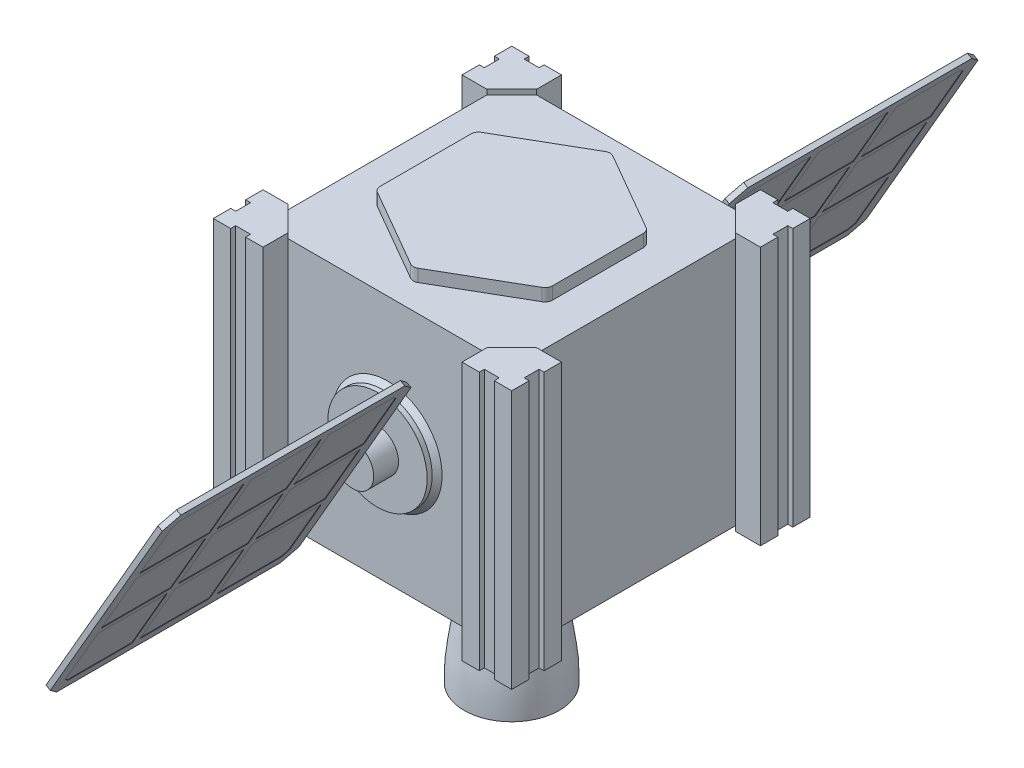
SolidWorks part; units mm, degrees
ref_plane "Front Plane" through (0, 0, 0) normal (0, 0, 1) x (1, 0, 0)
ref_plane "Top Plane" through (0, 0, 0) normal (0, 1, 0) x (1, 0, 0)
ref_plane "Right Plane" through (0, 0, 0) normal (1, 0, 0) x (0, 0, -1)
sketch "Sketch2" plane through (0, 0, 0) normal (0, 1, 0) x (1, 0, 0)
  line L1 (63.5, -63.5) -> (-63.5, -63.5)
  line L2 (63.5, -63.5) -> (63.5, 63.5)
  line L3 (63.5, 63.5) -> (-63.5, 63.5)
  line L4 (-63.5, -63.5) -> (-63.5, 63.5)
  line L5 (63.5, -63.5) -> (-63.5, 63.5) construction
  line L6 (63.5, 63.5) -> (-63.5, -63.5) construction
  line L7 (-50.8, 50.8) -> (-76.2, 50.8)
  line L8 (-50.8, 50.8) -> (-50.8, 76.2)
  line L9 (-50.8, 76.2) -> (-76.2, 76.2)
  line L10 (-76.2, 50.8) -> (-76.2, 76.2)
  line L11 (-50.8, 50.8) -> (-76.2, 76.2) construction
  line L12 (-50.8, 76.2) -> (-76.2, 50.8) construction
  line L13 (50.8, 50.8) -> (76.2, 50.8)
  line L14 (50.8, 50.8) -> (50.8, 76.2)
  line L15 (50.8, 76.2) -> (76.2, 76.2)
  line L16 (76.2, 50.8) -> (76.2, 76.2)
  line L17 (50.8, 50.8) -> (76.2, 76.2) construction
  line L18 (50.8, 76.2) -> (76.2, 50.8) construction
  line L19 (76.2, -50.8) -> (50.8, -50.8)
  line L20 (76.2, -50.8) -> (76.2, -76.2)
  line L21 (76.2, -76.2) -> (50.8, -76.2)
  line L22 (50.8, -50.8) -> (50.8, -76.2)
  line L23 (76.2, -50.8) -> (50.8, -76.2) construction
  line L24 (76.2, -76.2) -> (50.8, -50.8) construction
  line L25 (-50.8, -50.8) -> (-76.2, -50.8)
  line L26 (-50.8, -50.8) -> (-50.8, -76.2)
  line L27 (-50.8, -76.2) -> (-76.2, -76.2)
  line L28 (-76.2, -50.8) -> (-76.2, -76.2)
  line L29 (-50.8, -50.8) -> (-76.2, -76.2) construction
  line L30 (-50.8, -76.2) -> (-76.2, -50.8) construction
  point P0 (0, 0)
  dimension "D1" = 25.4
  dimension "D2" = 25.4
  dimension "D3" = 127
  dimension "D4" = 127
  dimension "D5" = 25.4
  dimension "D6" = 25.4
  dimension "D7" = 25.4
extrude "Boss-Extrude1" add sketch "Sketch2" along normal blind 127 contours L10 L7 L4 L3 L8 L9 | L7 L8 L3 L4 | L14 L13 L2 L3 | L13 L16 L15 L14 L3 L2 | L1 L22 L21 L20 L19 L2 | L25 L28 L27 L26 L1 L4 | L26 L25 L4 L1 | L25 L26 L1 L22 L19 L2 L13 L14 L3 L8 L7 L4 | L19 L22 L1 L2 region at (65.6167, 0, 65.6167) region at (57.15, 0, 57.15) region at (0, 0, 0) region at (-65.6167, 0, 65.6167) region at (-57.15, 0, 57.15) region at (57.15, 0, -57.15) region at (65.6167, 0, -65.6167) region at (-65.6167, 0, -65.6167) region at (-57.15, 0, -57.15)
sketch "Sketch3" plane through (0, 0, 0) normal (0, -1, 0) x (1, 0, 0)
  line L0 (-50.8, 63.5) -> (-63.5, 50.8)
  line L1 (50.8, 63.5) -> (63.5, 50.8)
  line L2 (63.5, -50.8) -> (50.8, -63.5)
  line L3 (-63.5, -50.8) -> (-50.8, -63.5)
  line L20 (-63.5, 50.8) -> (-63.5, -50.8)
  line L21 (-63.5, -50.8) -> (-76.2, -50.8)
  line L22 (-76.2, -50.8) -> (-76.2, -76.2)
  line L23 (-76.2, -76.2) -> (-50.8, -76.2)
  line L24 (-50.8, -76.2) -> (-50.8, -63.5)
  line L25 (-50.8, -63.5) -> (50.8, -63.5)
  line L26 (50.8, -63.5) -> (50.8, -76.2)
  line L27 (50.8, -76.2) -> (76.2, -76.2)
  line L28 (76.2, -76.2) -> (76.2, -50.8)
  line L29 (76.2, -50.8) -> (63.5, -50.8)
  line L30 (63.5, -50.8) -> (63.5, 50.8)
  line L31 (63.5, 50.8) -> (76.2, 50.8)
  line L32 (76.2, 50.8) -> (76.2, 76.2)
  line L33 (76.2, 76.2) -> (50.8, 76.2)
  line L34 (50.8, 76.2) -> (50.8, 63.5)
  line L35 (50.8, 63.5) -> (-50.8, 63.5)
  line L36 (-50.8, 63.5) -> (-50.8, 76.2)
  line L37 (-50.8, 76.2) -> (-76.2, 76.2)
  line L38 (-76.2, 76.2) -> (-76.2, 50.8)
  line L39 (-76.2, 50.8) -> (-63.5, 50.8)
  line L40 (-63.5, 50.8) -> (-63.5, -50.8)
  line L41 (-63.5, -50.8) -> (-76.2, -50.8)
  line L42 (-76.2, -50.8) -> (-76.2, -76.2)
  line L43 (-76.2, -76.2) -> (-50.8, -76.2)
  line L44 (-50.8, -76.2) -> (-50.8, -63.5)
  line L45 (-50.8, -63.5) -> (50.8, -63.5)
  line L46 (50.8, -63.5) -> (50.8, -76.2)
  line L47 (50.8, -76.2) -> (76.2, -76.2)
  line L48 (76.2, -76.2) -> (76.2, -50.8)
  line L49 (76.2, -50.8) -> (63.5, -50.8)
  line L50 (63.5, -50.8) -> (63.5, 50.8)
  line L51 (63.5, 50.8) -> (76.2, 50.8)
  line L52 (76.2, 50.8) -> (76.2, 76.2)
  line L53 (76.2, 76.2) -> (50.8, 76.2)
  line L54 (50.8, 76.2) -> (50.8, 63.5)
  line L55 (50.8, 63.5) -> (-50.8, 63.5)
  line L56 (-50.8, 63.5) -> (-50.8, 76.2)
  line L57 (-50.8, 76.2) -> (-76.2, 76.2)
  line L58 (-76.2, 76.2) -> (-76.2, 50.8)
  line L59 (-76.2, 50.8) -> (-63.5, 50.8)
  arc A0 (-50.8, -63.5) -> (-50.8, -65.3363) centre (-51.7181, -64.4181) cw
  line M22 (-63.5, -50.8) -> (-76.2, -50.8)
  line M23 (-76.2, -50.8) -> (-76.2, -76.2)
  line M24 (-76.2, -76.2) -> (-50.8, -76.2)
  line M25 (-50.8, -76.2) -> (-50.8, -63.5)
  line M27 (50.8, -63.5) -> (50.8, -76.2)
  line M28 (50.8, -76.2) -> (76.2, -76.2)
  line M29 (76.2, -76.2) -> (76.2, -50.8)
  line M30 (76.2, -50.8) -> (63.5, -50.8)
  line M32 (63.5, 50.8) -> (76.2, 50.8)
  line M33 (76.2, 50.8) -> (76.2, 76.2)
  line M34 (76.2, 76.2) -> (50.8, 76.2)
  line M35 (50.8, 76.2) -> (50.8, 63.5)
  line M37 (-50.8, 63.5) -> (-50.8, 76.2)
  line M38 (-50.8, 76.2) -> (-76.2, 76.2)
  line M39 (-76.2, 76.2) -> (-76.2, 50.8)
  line M40 (-76.2, 50.8) -> (-63.5, 50.8)
  dimension "D1" = 0
extrude "Boss-Extrude2" add sketch "Sketch3" along normal blind 2.54 contours L0 M37 M38 M39 M40 | L1 M35 M32 M33 M34 | L2 M30 M27 M28 M29 | L3 L44 M22 M23 M24 M25 region at (-64.7095, 0, 64.7095) region at (64.7095, 0, 64.7095) region at (-64.7095, 0, -64.7095) region at (64.7095, 0, -64.7095)
ref_plane "Plane1" through (0, 63.5, 0) normal (0, 1, 0) x (1, 0, 0)
mirror "Mirror1" about plane through (0, 63.5, 0) normal (0, 1, 0) of "Boss-Extrude2"
sketch "Sketch5" plane through (0, 129.54, 0) normal (0, 1, 0) x (1, 0, 0)
  line L0 (-76.2, 76.2) -> (-50.8, 76.2) construction
  line L1 (-67.31, 76.2) -> (-59.69, 76.2)
  line L2 (-67.31, 76.2) -> (-67.31, 73.66)
  line L3 (-67.31, 73.66) -> (-59.69, 73.66)
  line L4 (-59.69, 76.2) -> (-59.69, 73.66)
  line L5 (-76.2, 50.8) -> (-76.2, 76.2) construction
  line L6 (-76.2, 67.31) -> (-73.66, 67.31)
  line L7 (-76.2, 67.31) -> (-76.2, 59.69)
  line L8 (-76.2, 59.69) -> (-73.66, 59.69)
  line L9 (-73.66, 67.31) -> (-73.66, 59.69)
  line L10 (-50.8, 63.5) -> (-73.66, 63.5) construction
  line L12 (-63.5, 50.8) -> (-63.5, 73.66) construction
  line L13 (-50.8, 76.2) -> (-50.8, 63.5) construction
  line L15 (-63.5, 50.8) -> (-76.2, 50.8) construction
  dimension "D1" = 7.62
  dimension "D2" = 2.54
extrude "Cut-Extrude1" cut sketch "Sketch5" against normal through all
ref_axis "Axis1" through (0, 136.144, 0) along (0, -1, 0)
pattern_circular "CirPattern1" count 4 over 360 about axis through (0, 136.144, 0) along (0, -1, 0) of "Cut-Extrude1"
sketch "Sketch6" plane through (0, 0, 63.5) normal (0, 0, 1) x (1, 0, 0)
  line L0 (0, 127) -> (0, -3.9486) construction
  line L1 (50.8, 127) -> (-50.8, 127) construction
  circle A0 centre (0, 61.5257) radius 25.4
  dimension "D1" = 50.8
extrude "Boss-Extrude3" add sketch "Sketch6" along normal blind 5.08
chamfer "Chamfer1" distance 2.54 angle 45 1 edges at (25.4, 61.5257, 63.5)
sketch "Sketch7" plane through (0, 0, 68.58) normal (0, 0, 1) x (1, 0, 0)
  line L0 (0, 86.9257) -> (0, 36.1257) construction
  circle A0 centre (0, 61.5257) radius 25.4 construction
  circle A1 centre (0, 61.5257) radius 10.795
  dimension "D1" = 21.59
extrude "Boss-Extrude4" add sketch "Sketch7" along normal blind 12.7
sketch "Sketch8" plane through (0, 0, 81.28) normal (0, 0, 1) x (1, 0, 0)
  line L0 (0, 71.6598) -> (0, 50.7307) construction
  line L1 (0, 61.1953) -> (9.2024, 55.8823) construction
  circle A0 centre (0, 61.5257) radius 10.795 construction
  circle A1 centre (0, 61.5257) radius 10.795 construction
  dimension "D1" = 60
ref_plane "Plane2" through (0, 61.1953, 81.28) normal (0.866, -0.5, 0) x (-0.5, -0.866, 0)
sketch "Sketch9" plane through (0, 61.1953, 81.28) normal (0.866, -0.5, 0) x (-0.5, -0.866, 0)
  line L0 (-11.0812, 0) -> (10.5088, 0) construction
  line L1 (-11.0812, 0) -> (10.5088, 0) construction
  line L2 (-0.2862, 0) -> (-63.7862, 0)
  line L3 (-0.2862, 0) -> (63.2138, 0)
  line L4 (-63.7862, 0) -> (-63.7862, -127)
  line L5 (-63.7862, -127) -> (63.2138, -127)
  line L6 (63.2138, -127) -> (63.2138, 0)
  dimension "D1" = 63.5
  dimension "D2" = 63.5
  dimension "D3" = 127
extrude "Boss-Extrude5" add sketch "Sketch9" along normal blind 1.27 and the other way blind 1.27
chamfer "Chamfer2" distance 6.35 angle 45 4 edges at (-31.6069, 6.4505, 81.28) (31.8931, 116.4357, 81.28) (31.8931, 116.4357, 208.28) (-31.6069, 6.4505, 208.28)
sketch "Sketch11" plane through (-27.5982, 15.9338, 0) normal (-0.866, 0.5, 0) x (0, 0, 1)
  line L0 (87.63, 53.2828) -> (123.19, 53.2828) construction
  line L1 (123.19, 53.2828) -> (127, 53.2828) construction
  line L2 (127, 53.2828) -> (162.56, 53.2828) construction
  line L3 (162.56, 53.2828) -> (166.37, 53.2828) construction
  line L4 (166.37, 53.2828) -> (201.93, 53.2828) construction
  line L5 (144.78, 110.4328) -> (144.78, 74.8728) construction
  line L7 (87.63, 64.0211) -> (87.63, 42.5445)
  line L10 (127, 74.8728) -> (123.19, 74.8728) construction
  line L11 (87.63, 71.0628) -> (123.19, 71.0628)
  line L16 (87.63, 71.0628) -> (87.63, 35.5028)
  line L17 (87.63, 35.5028) -> (123.19, 35.5028)
  line L22 (123.19, 71.0628) -> (123.19, 35.5028)
  line L23 (87.63, 71.0628) -> (123.19, 35.5028) construction
  line L24 (144.78, 74.8728) -> (144.78, 71.0628) construction
  line L25 (144.78, 71.0628) -> (144.78, 35.5028) construction
  line L26 (144.78, 35.5028) -> (144.78, 31.6928) construction
  line L27 (144.78, 31.6928) -> (144.78, -3.8672) construction
  line L28 (87.63, 35.5028) -> (123.19, 71.0628) construction
  line L29 (162.56, 71.0628) -> (127, 71.0628)
  line L30 (162.56, 71.0628) -> (162.56, 35.5028)
  line L31 (162.56, 35.5028) -> (127, 35.5028)
  line L32 (127, 71.0628) -> (127, 35.5028)
  line L33 (162.56, 71.0628) -> (127, 35.5028) construction
  line L34 (162.56, 35.5028) -> (127, 71.0628) construction
  line L36 (201.93, 71.0628) -> (201.93, 35.5028)
  line L39 (201.93, 71.0628) -> (166.37, 71.0628)
  line L40 (201.93, 71.0628) -> (201.93, 35.5028)
  line L41 (201.93, 35.5028) -> (166.37, 35.5028)
  line L42 (166.37, 71.0628) -> (166.37, 35.5028)
  line L43 (201.93, 71.0628) -> (166.37, 35.5028) construction
  line L44 (201.93, 35.5028) -> (166.37, 71.0628) construction
  line L45 (87.63, 64.0211) -> (87.63, 42.5445)
  line L46 (127, -3.8672) -> (162.56, -3.8672)
  line L47 (127, -3.8672) -> (127, 31.6928)
  line L48 (127, 31.6928) -> (162.56, 31.6928)
  line L49 (162.56, -3.8672) -> (162.56, 31.6928)
  line L50 (127, -3.8672) -> (162.56, 31.6928) construction
  line L51 (127, 31.6928) -> (162.56, -3.8672) construction
  line L52 (127, 74.8728) -> (162.56, 74.8728)
  line L53 (127, 74.8728) -> (127, 110.4328)
  line L54 (199.2997, 110.4328) -> (201.93, 107.8026)
  line L55 (201.93, 107.8026) -> (201.93, -1.2369)
  line L56 (201.93, -1.2369) -> (199.2997, -3.8672)
  line L57 (199.2997, -3.8672) -> (90.2603, -3.8672)
  line L58 (90.2603, -3.8672) -> (87.63, -1.2369)
  line L59 (87.63, -1.2369) -> (87.63, 42.5445)
  line L60 (87.63, 64.0211) -> (87.63, 107.8026)
  line L61 (87.63, 107.8026) -> (90.2603, 110.4328)
  line L62 (90.2603, 110.4328) -> (199.2997, 110.4328)
  line L63 (199.2997, 110.4328) -> (201.93, 107.8026)
  line L64 (201.93, 107.8026) -> (201.93, -1.2369)
  line L65 (201.93, -1.2369) -> (199.2997, -3.8672)
  line L66 (199.2997, -3.8672) -> (90.2603, -3.8672)
  line L67 (90.2603, -3.8672) -> (87.63, -1.2369)
  line L68 (87.63, -1.2369) -> (87.63, 42.5445)
  line L69 (87.63, 64.0211) -> (87.63, 107.8026)
  line L70 (87.63, 107.8026) -> (90.2603, 110.4328)
  line L71 (90.2603, 110.4328) -> (199.2997, 110.4328)
  line L72 (127, 110.4328) -> (162.56, 110.4328)
  line L73 (162.56, 74.8728) -> (162.56, 110.4328)
  line L74 (127, 74.8728) -> (162.56, 110.4328) construction
  line L75 (127, 110.4328) -> (162.56, 74.8728) construction
  line L76 (123.19, 74.8728) -> (123.19, 71.0628) construction
  point P2 (144.78, 53.2828)
  point P7 (105.41, 53.2828)
  point P8 (105.41, 53.2828)
  point P13 (144.78, 53.2828)
  point P14 (184.15, 53.2828)
  point P27 (184.15, 53.2828)
  point P28 (184.15, 53.2828)
  point P33 (144.78, 13.9128)
  point P38 (144.78, 92.6528)
  dimension "D2" = 3.81
  dimension "D1" = 6.35
extrude "Cut-Extrude2" cut sketch "Sketch11" against normal blind 0.254 contours L52 L73 L71 L53 | L22 L11 L16 L7 L17 | L29 L32 L31 L30 | L39 L42 L41 L36 | L46 L49 L48 L47 region at (-0.9568, 62.0781, 105.41) region at (18.7282, 96.1735, 144.78) region at (-20.6418, 27.9827, 144.78) region at (-0.9568, 62.0781, 184.15) region at (-0.9568, 62.0781, 144.78)
sketch "Sketch12" plane through (-27.5982, 15.9338, 0) normal (-0.866, 0.5, 0) x (0, 0, 1)
  line L0 (127, 110.4328) -> (162.56, 110.4328) construction
  line L1 (87.63, 71.0628) -> (87.63, 35.5028) construction
  line L11 (127, 74.8728) -> (123.19, 74.8728) construction
  line L12 (92.1201, 112.2927) -> (85.7701, 105.9427)
  line L13 (92.1201, 112.2927) -> (85.7701, 105.9427)
  line L14 (123.19, 74.8728) -> (123.19, 71.0628) construction
  line L16 (123.19, 74.8728) -> (87.63, 74.8728)
  line L17 (123.19, 74.8728) -> (123.19, 110.4328)
  line L18 (123.19, 110.4328) -> (87.63, 110.4328)
  line L19 (87.63, 74.8728) -> (87.63, 110.4328)
  dimension "D1" = 6.35
extrude "Cut-Extrude4" cut sketch "Sketch12" against normal blind 0.254 contours L19 L16 L17 L18 L13 region at (18.7051, 96.1334, 105.4564)
ref_plane "Plane3" through (26.6414, 46.1443, 0) normal (0.5, 0.866, 0) x (0.866, -0.5, 0)
ref_plane "Plane4" through (0, 0, 144.78) normal (0, 0, 1) x (1, 0, 0)
ref_axis "Axis2" through (-53.4431, 92.3811, 144.78) along (0.866, -0.5, 0)
pattern_circular "CirPattern2" count 4 over 360 about axis through (-53.4431, 92.3811, 144.78) along (0.866, -0.5, 0) of "Cut-Extrude4"
mirror "Mirror2" about plane through (0, 61.1953, 81.28) normal (0.866, -0.5, 0) of "CirPattern2", "Cut-Extrude4", "Cut-Extrude2"
mirror "Mirror3" about plane through (0, 0, 0) normal (0, 0, 1) of "Mirror2", "CirPattern2", "Boss-Extrude3", "Boss-Extrude4", "Boss-Extrude5", "Chamfer2", "Cut-Extrude2", "Cut-Extrude4"
sketch "Sketch13" plane through (0, 0, 0) normal (1, 0, 0) x (0, 0, -1)
  line L0 (-102.5088, -52.1221) -> (-280.5088, -52.1221) construction
  line L1 (0, 0) -> (5.5983, 0) construction
  line L2 (-50.8, 0) -> (50.8, 0) construction
  line L3 (24.3386, -75.8591) -> (17.9886, -75.8596)
  line L4 (11.9857, 0) -> (5.5983, 0)
  line L5 (0, 0) -> (0, -75.8596) construction
  line L6 (0, 6.35) -> (12.6767, 6.35) construction
  spline S0 degree 3 poles (5.5983, 0) (5.276, -2.9616) (6.2182, -7.7173) (8.104, -13.8696) (8.5901, -18.7682) (10.529, -23.7585) (11.2236, -29.2333) (12.6866, -34.8081) (13.9106, -40.5125) (15.2007, -46.5877) (16.2352, -54.9113) (17.7979, -63.22) (18.0112, -70.8129) (17.9884, -74.5422) (17.9886, -75.8596) knots 0 0 0 0 0.11445 0.186777 0.250223 0.304458 0.393661 0.463685 0.528614 0.620645 0.705118 0.854855 0.948747 1 1 1 1
  spline S1 degree 1 poles (12.6767, 6.35) (24.3386, -75.8591) knots 0 0 1 1 construction
  spline S2 degree 3 poles (12.6767, 6.35) (12.5807, 5.468) (12.4367, 4.1448) (12.2449, 2.3817) (12.1247, 1.2771) (12.0418, 0.5147) (12.0001, 0.1321) (11.9762, -0.0882) (11.9515, -0.3144) (11.9311, -0.5027) (11.911, -0.6864) (11.905, -0.7428) (11.8936, -0.8591) (11.8806, -1.018) (11.8567, -1.4126) (11.8509, -2.0255) (11.9066, -2.9057) (12.0259, -3.8498) (12.2671, -5.1968) (12.7054, -7.0205) (13.2912, -9.0866) (13.7819, -10.9534) (14.1353, -12.4697) (14.4241, -14.0718) (14.6269, -15.4103) (14.7819, -16.353) (14.9093, -16.9953) (15.0032, -17.4042) (15.1143, -17.8148) (15.3111, -18.4682) (15.6313, -19.4353) (16.0188, -20.6226) (16.3267, -21.713) (16.7223, -23.2828) (17.1456, -25.4872) (17.5044, -27.6042) (17.8044, -29.0742) (18.1625, -30.6413) (18.6866, -32.7368) (19.322, -35.4675) (19.8804, -38.0712) (20.4333, -40.657) (20.9781, -43.3345) (21.4773, -46.127) (21.877, -48.8664) (22.2298, -51.4618) (22.7252, -54.7623) (23.3091, -58.2847) (23.8103, -61.9687) (24.1974, -65.8293) (24.33, -69.6019) (24.3459, -73.2575) (24.3385, -74.9834) (24.3386, -75.8591) knots -0.090645 -0.090645 -0.090645 -0.090645 -0.056562 -0.039521 -0.022479 -0.013959 -0.009913 -0.007783 -0.005438 -0.001178 -0.000113 0.000953 0.003083 0.007343 0.011603 0.028645 0.045686 0.062727 0.079769 0.113851 0.147934 0.164975 0.182017 0.199058 0.216099 0.233141 0.241661 0.250182 0.258703 0.267223 0.284264 0.301306 0.309826 0.318347 0.35243 0.386512 0.403554 0.420595 0.454678 0.48876 0.522843 0.556926 0.591008 0.625091 0.659174 0.693256 0.727339 0.795504 0.829587 0.863669 0.931835 0.965917 1 1 1 1 only from (11.9857, 0) to (24.3386, -75.8591)
  dimension "D1" = 6.35
revolve "Revolve2" add sketch "Sketch13" angle 360 about L5 reverse direction yes
chamfer "Chamfer3" distance 6.35 angle 45 1 edges at (0, 0, -11.9857) first distance on face at (0, 0, -11.9857)
sketch "Sketch14" plane through (0, 127, 0) normal (0, 1, 0) x (1, 0, 0)
  line L0 (63.5, -50.8) -> (63.5, 50.8) construction
  line L1 (43.9941, 25.4) -> (0, 50.8)
  line L2 (0, 50.8) -> (-43.9941, 25.4)
  line L3 (-43.9941, 25.4) -> (-43.9941, -25.4)
  line L4 (-43.9941, -25.4) -> (0, -50.8)
  line L5 (0, -50.8) -> (43.9941, -25.4)
  line L6 (43.9941, -25.4) -> (43.9941, 25.4)
  circle A0 centre (0, 0) radius 43.9941 construction
  dimension "D1" = 50.8
extrude "Boss-Extrude6" add sketch "Sketch14" along normal blind 6.35 contours L1 L2 L3 L4 L5 L6
fillet "Fillet1" radius 3.81 6 edges at (-43.9941, 130.175, 25.4) (43.9941, 130.175, -25.4) (-43.9941, 130.175, -25.4) (0, 130.175, 50.8) (43.9941, 130.175, 25.4) (0, 130.175, -50.8)
sketch "Sketch15" plane through (63.5, 0, 0) normal (1, 0, 0) x (0, 0, -1)
  line L0 (0, 0) -> (0, 127) construction
  line L1 (-50.8, 127) -> (50.8, 127) construction
  line L2 (0, 63.5) -> (38.8726, 109.8265) construction
  dimension "D1" = 40
